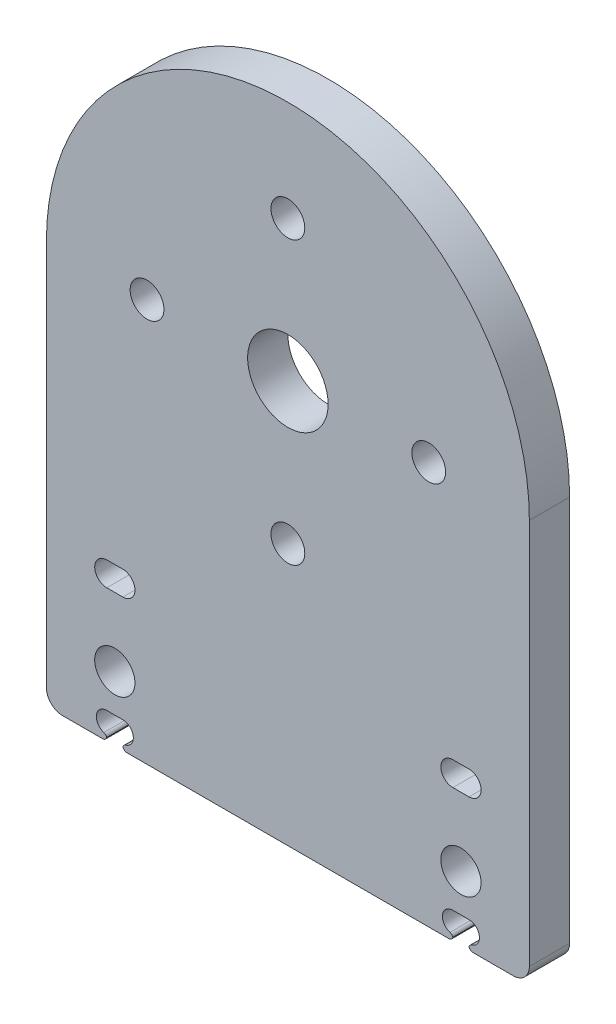
SolidWorks part; units mm, degrees
ref_plane "Front Plane" through (0, 0, 0) normal (0, 0, 1) x (1, 0, 0)
ref_plane "Top Plane" through (0, 0, 0) normal (0, 1, 0) x (1, 0, 0)
ref_plane "Right Plane" through (0, 0, 0) normal (1, 0, 0) x (0, 0, -1)
sketch "Sketch1" plane through (0, 0, 0) normal (0, 0, 1) x (1, 0, 0)
  line L0 (20.5, -7) -> (22.5, -7) construction
  line L1 (-30, -25) -> (-22.5, -25)
  line L2 (-30, -25) -> (-30, 25)
  line L3 (-30, 25) -> (30, 25)
  line L4 (30, -25) -> (30, 25)
  line L5 (0, 25) -> (0, -25) construction
  line L6 (-30, 0) -> (30, 0) construction
  line L7 (20.5, -5.5) -> (22.5, -5.5)
  line L8 (20.5, -8.5) -> (22.5, -8.5)
  line L9 (20.5, -23) -> (22.5, -23) construction
  line L10 (20.5, -21.7) -> (22.5, -21.7)
  line L12 (-20.5, -7) -> (-22.5, -7) construction
  line L13 (-20.5, -5.5) -> (-22.5, -5.5)
  line L14 (-20.5, -8.5) -> (-22.5, -8.5)
  line L15 (-20.5, -23) -> (-22.5, -23) construction
  line L16 (-20.5, -21.7) -> (-22.5, -21.7)
  line L18 (-22.5, -24.3) -> (-22.5, -25)
  line L19 (-20.5, -24.3) -> (-20.5, -25)
  line L20 (20.5, -24.3) -> (20.5, -25)
  line L21 (22.5, -24.3) -> (22.5, -25)
  line L22 (22.5, -25) -> (30, -25)
  line L23 (-20.5, -25) -> (20.5, -25)
  arc A1 (30, 25) -> (-30, 25) centre (0, 25) ccw
  circle A2 centre (21.5, -17) radius 2.5
  arc A3 (20.5, -5.5) -> (20.5, -8.5) centre (20.5, -7) ccw
  arc A4 (22.5, -8.5) -> (22.5, -5.5) centre (22.5, -7) ccw
  arc A5 (20.5, -21.7) -> (20.5, -24.3) centre (20.5, -23) ccw
  arc A6 (22.5, -24.3) -> (22.5, -21.7) centre (22.5, -23) ccw
  arc A7 (-20.5, -5.5) -> (-20.5, -8.5) centre (-20.5, -7) cw
  arc A8 (-22.5, -8.5) -> (-22.5, -5.5) centre (-22.5, -7) cw
  arc A9 (-20.5, -21.7) -> (-20.5, -24.3) centre (-20.5, -23) cw
  arc A10 (-22.5, -24.3) -> (-22.5, -21.7) centre (-22.5, -23) cw
  circle A11 centre (-21.5, -17) radius 2.5
  point P0 (0, 0)
  point P8 (21.5, -7)
  point P15 (21.5, -23)
  point P25 (-21.5, -7)
  point P32 (-21.5, -23)
  dimension "D3" = 5
  dimension "D8" = 1.5
  dimension "D11" = 2
  dimension "D10" = 1.3
  dimension "D1" = 60
  dimension "D2" = 50
  dimension "D4" = 2
  dimension "D5" = 8.5
  dimension "D6" = 10
  dimension "D7" = 6
  dimension "D9" = 2
extrude "Boss-Extrude1" add sketch "Sketch1" along normal mid plane 5 contours L1 L4 L3 L2 | L3 A1 region at (0, 0.482, 0) region at (0, 37.7324, 0)
sketch "Sketch2" plane through (0, 0, 2.5) normal (0, 0, 1) x (1, 0, 0)
  line L0 (-30, -25) -> (-22.5, -25) construction
  line L2 (-17.5, 7.5) -> (17.5, 7.5)
  line L3 (-17.5, 7.5) -> (-17.5, 42.5)
  line L4 (-17.5, 42.5) -> (17.5, 42.5)
  line L5 (17.5, 7.5) -> (17.5, 42.5)
  line L6 (0, 42.5) -> (0, 7.5) construction
  line L7 (-17.5, 25) -> (17.5, 25) construction
  circle A0 centre (0, 25) radius 5
  circle A1 centre (0, 42.5) radius 2.1
  circle A2 centre (17.5, 25) radius 2.1
  circle A3 centre (0, 7.5) radius 2.1
  circle A4 centre (-17.5, 25) radius 2.1
  circle A5 centre (0, 25) radius 17.5 construction
  dimension "D2" = 10
  dimension "D5" = 4.2
  dimension "D1" = 50
  dimension "D3" = 35
  dimension "D4" = 17.5
extrude "Cut-Extrude1" cut sketch "Sketch2" against normal blind 5 contours A0 | L3 A4 | L3 A4 | L5 A2 | L5 A2 | L4 A1 | L4 A1 | L2 A3 | L2 A3 region at (0, 6.6087, 2.5) region at (0, 8.3913, 2.5) region at (16.6087, 25, 2.5) region at (18.3913, 25, 2.5) region at (-18.3913, 25, 2.5) region at (-16.6087, 25, 2.5) region at (0, 41.6087, 2.5) region at (0, 43.3913, 2.5) region at (0, 25, 2.5)
fillet "Fillet1" radius 0.5 8 edges at (22.5, -25, 0) (20.5, -25, 0) (22.5, -24.3, 0) (20.5, -24.3, 0) (-20.5, -24.3, 0) (-20.5, -25, 0) (-22.5, -25, 0) (-22.5, -24.3, 0)
fillet "Fillet2" radius 2 2 edges at (-30, -25, 0) (30, -25, 0)
